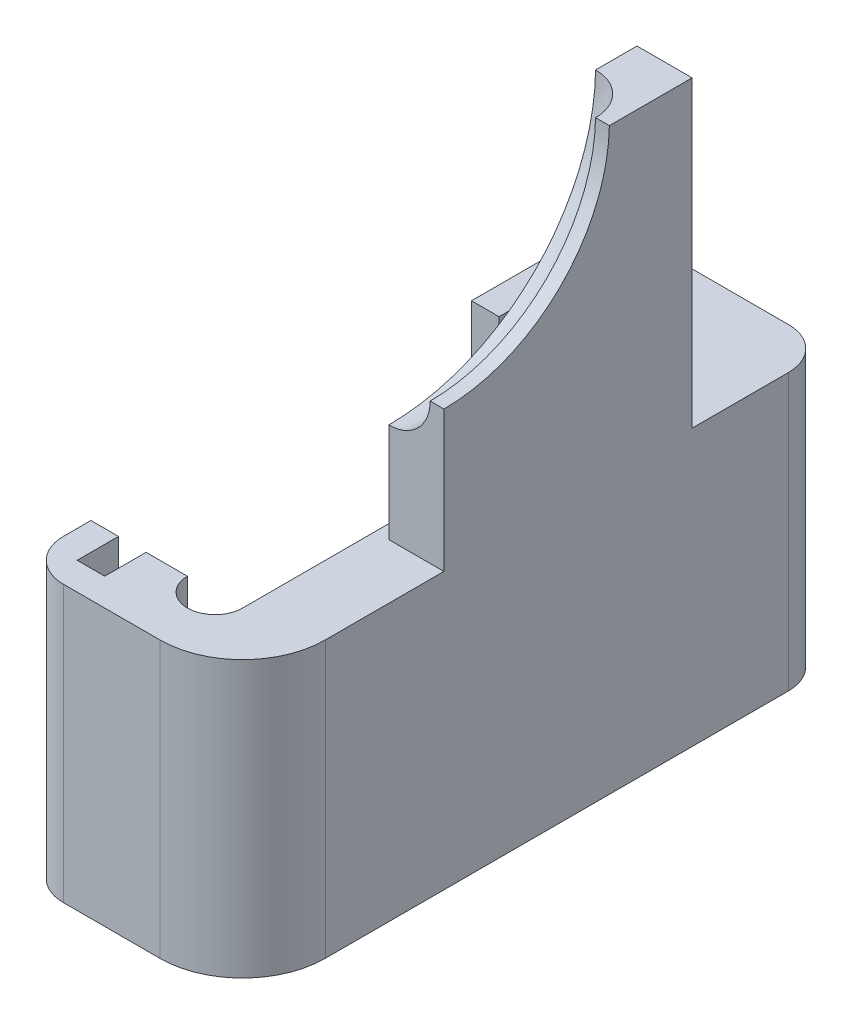
SolidWorks part; units mm, degrees
note: The reader was unsure of these and kept them because the rebuilt part matched: shared geometry of "Sketch9<3>".
ref_plane "Front Plane" through (0, 0, 0) normal (0, 0, 1) x (1, 0, 0)
ref_plane "Top Plane" through (0, 0, 0) normal (0, 1, 0) x (1, 0, 0)
ref_plane "Right Plane" through (0, 0, 0) normal (1, 0, 0) x (0, 0, -1)
sketch "Sketch1" plane through (0, 0, 0) normal (0, 1, 0) x (1, 0, 0)
  line L0 (0, 15.3) -> (0, -12.3)
  line L1 (0, 15.3) -> (-2, 15.3) construction
  line L2 (0, -12.3) -> (-2, -12.3) construction
  line L3 (5, 20.3) -> (5, -17.3)
  line L4 (-4, 15.3) -> (-7, 15.3)
  line L5 (-4, -12.3) -> (-7, -12.3)
  line L6 (-7, 15.3) -> (-7, 20.3)
  line L7 (-7, -12.3) -> (-7, -17.3)
  line L8 (-7, -17.3) -> (5, -17.3)
  line L9 (-7, 20.3) -> (5, 20.3)
  arc A0 (-4, 15.3) -> (0, 15.3) centre (-2, 15.3) cw
  arc A1 (0, -12.3) -> (-4, -12.3) centre (-2, -12.3) cw
  dimension "D5" = 2
  dimension "D6" = 5
  dimension "D1" = 27.6
  dimension "D2" = 15.3
  dimension "D3" = 2
  dimension "D4" = 2
  dimension "D7" = 37.6
  dimension "D8" = 5
  dimension "D9" = 3
  dimension "D10" = 3
  dimension "D11" = 5
  dimension "D12" = 7
  dimension "D13" = 5
  dimension "D14" = 7
extrude "Boss-Extrude1" add sketch "Sketch1" along normal blind 20 contours L0 A1 L5 L7 L8 L3 L9 L6 L4 A0
sketch "Sketch3" plane through (0, 0, -20.3) normal (0, 0, -1) x (-1, 0, 0)
  line L1 (-5, 20) -> (7, 20)
  line L2 (-5, 20) -> (-5, 0)
  line L3 (-5, 0) -> (7, 0)
  line L4 (7, 20) -> (7, 0)
extrude "Boss-Extrude2" add sketch "Sketch3" along normal blind 5
fillet "Fillet1" radius 6 1 edges at (5, 10, 17.3)
fillet "Fillet2" radius 3 1 edges at (5, 10, -25.3)
sketch "Sketch4" plane through (0, 0, -25.3) normal (0, 0, -1) x (-1, 0, 0)
  line L0 (-5, 0) -> (-5, 20) construction
  line L1 (-2, 0) -> (7, 0) construction
  circle A0 centre (0.5, 10) radius 2
  dimension "D1" = 4
  dimension "D2" = 5.5
  dimension "D3" = 10
extrude "Cut-Extrude1" cut sketch "Sketch4" against normal blind 6 contours A0
sketch "Sketch5" plane through (-7, 0, 0) normal (-1, 0, 0) x (0, 0, 1)
  line L0 (12.3, 0) -> (17.3, 0) construction
  line L1 (17.3, 20) -> (15.3, 20)
  line L2 (17.3, 20) -> (17.3, 0)
  line L3 (17.3, 0) -> (15.3, 0)
  line L4 (15.3, 20) -> (15.3, 0)
  line L5 (-15.3, 0) -> (-25.3, 0) construction
  line L6 (-25.3, 20) -> (-22.3, 20)
  line L7 (-25.3, 20) -> (-25.3, 0)
  line L8 (-25.3, 0) -> (-22.3, 0)
  line L9 (-22.3, 20) -> (-22.3, 0)
  dimension "D1" = 2
  dimension "D2" = 3
extrude "Boss-Extrude3" add sketch "Sketch5" along normal blind 4
sketch "Sketch6" plane through (0, 0, 15.3) normal (0, 0, -1) x (-1, 0, 0)
  line L0 (11, 0) -> (7, 0) construction
  line L1 (11, 20) -> (9, 20)
  line L2 (11, 20) -> (11, 0)
  line L3 (11, 0) -> (9, 0)
  line L4 (9, 20) -> (9, 0)
  dimension "D1" = 2
extrude "Boss-Extrude4" add sketch "Sketch6" along normal blind 3
sketch "Sketch7" plane through (0, 0, -22.3) normal (0, 0, 1) x (1, 0, 0)
  line L0 (-11, 0) -> (-1, 0) construction
  line L1 (-11, 20) -> (-9, 20)
  line L2 (-11, 20) -> (-11, 0)
  line L3 (-11, 0) -> (-9, 0)
  line L4 (-9, 20) -> (-9, 0)
  dimension "D1" = 2
extrude "Boss-Extrude5" add sketch "Sketch7" along normal up to surface (7 mm away) up to face at (-5.5, 10, -15.3)
fillet "Fillet3" radius 3 2 edges at (-11, 10, 17.3) (-11, 10, -25.3)
sketch "Sketch8" plane through (0, 0, 0) normal (-1, 0, 0) x (0, 0, 1)
  line L1 (-15.3, 0) -> (2.7, 0)
  line L2 (-15.3, 0) -> (-15.3, -22)
  line L3 (-15.3, -22) -> (2.7, -22)
  line L4 (2.7, 0) -> (2.7, -22)
  dimension "D1" = 18
  dimension "D2" = 22
extrude "Boss-Extrude6" add sketch "Sketch8" against normal blind 5 contours L2 L3 L4 L1
sketch "Sketch9" plane through (0, 0, 0) normal (-1, 0, 0) x (0, 0, 1)
  line L0 (2.7, 0) -> (12.3, 0) construction
  line L1 (-15.3, 0) -> (-15.3, -22) construction
  line L2 (2.7, 0) -> (2.7, -22) construction
  line L3 (-15.3, -22) -> (2.7, -22) construction
  arc A0 (2.7, -7.2) -> (-12.2987, -22) centre (2.7, -22.2) ccw
  arc A1 (2.7, -10.2) -> (-9.2983, -22) centre (2.7, -22.2) ccw
  point P0 (2.7, -22.2)
  line M3 (-15.3, -22) -> (2.7, -22)
  line M4 (2.7, -22) -> (2.7, 0)
  dimension "D3" = 15
  dimension "D4" = 12
  dimension "D1" = 22.2
  dimension "D2" = 18
extrude "Cut-Extrude2" cut sketch "Sketch9" against normal blind 4 and the other way through all contours A0 M4 M3
extrude "Cut-Extrude3" cut sketch "Sketch9<3>" against normal through all and the other way through all contours A1
sketch "Sketch9<3>" plane through (0, 0, 0) normal (-1, 0, 0) x (0, 0, 1) same geometry as "Sketch9"
fillet "Fillet4" radius 3 1 edges at (4, -11.5229, -7.8357)
sketch "Sketch11" plane through (0, 0, 0) normal (-1, 0, 0) x (0, 0, 1)
  line L1 (-15.3, -22) -> (2.7, -22)
  line L2 (-15.3, -22) -> (-15.3, 0)
  line L3 (-15.3, 0) -> (2.7, 0)
  line L4 (2.7, -22) -> (2.7, 0)
extrude "Cut-Extrude4" cut sketch "Sketch11" against normal blind 1
fillet "Fillet5" radius 3 2 edges at (3, 0, -15.3) (3, 0, 2.7)
ref_plane "Plane1" through (0, 10, 0) normal (0, -1, 0) x (-1, 0, 0)
mirror "Mirror1" about plane through (0, 10, 0) normal (0, -1, 0) of "Cut-Extrude4", "Fillet4", "Cut-Extrude2", "Cut-Extrude3", "Boss-Extrude6"
sketch "Sketch12" plane through (0, -22, 0) normal (0, -1, 0) x (1, 0, 0)
  line L1 (-6.7936, 14.3595) -> (9.2099, 14.3595)
  line L2 (-6.7936, 14.3595) -> (-6.7936, -18.735)
  line L3 (-6.7936, -18.735) -> (9.2099, -18.735)
  line L4 (9.2099, 14.3595) -> (9.2099, -18.735)
extrude "Cut-Extrude5" cut sketch "Sketch12" against normal up to surface (22 mm away) contours L4 L3 L2 L1 up to face at (-4.1684, 0, -3.4069)
